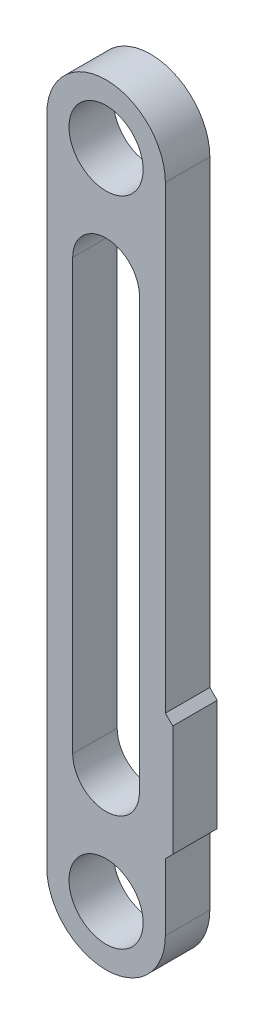
SolidWorks part; units mm, degrees
material "玻纤"
ref_plane "前视基准面" through (0, 0, 0) normal (0, 0, 1) x (1, 0, 0)
ref_plane "上视基准面" through (0, 0, 0) normal (0, 1, 0) x (1, 0, 0)
ref_plane "右视基准面" through (0, 0, 0) normal (1, 0, 0) x (0, 0, -1)
sketch "草图1" plane through (0, 0, 0) normal (0, 0, 1) x (1, 0, 0)
  line L0 (0, 0) -> (0, 88) construction
  line L1 (-8, 0) -> (-8, 88)
  line L2 (8, 0) -> (8, 88)
  arc A0 (-8, 0) -> (8, 0) centre (0, 0) ccw
  arc A1 (8, 88) -> (-8, 88) centre (0, 88) ccw
  circle A2 centre (0, 88) radius 5
  circle A3 centre (0, 0) radius 5
  point P3 (0, 44)
  dimension "D2" = 8
  dimension "D3" = 10
  dimension "D1" = 88
extrude "凸台-拉伸1" add sketch "草图1" along normal blind 6
sketch "草图2" plane through (0, 0, 0) normal (0, 0, -1) x (-1, 0, 0)
  line L0 (0, 73) -> (0, 15) construction
  line L1 (4.5, 73) -> (4.5, 15)
  line L2 (-4.5, 73) -> (-4.5, 15)
  line L3 (8, 88) -> (8, 0) construction
  arc A0 (4.5, 73) -> (-4.5, 73) centre (0, 73) ccw
  arc A1 (-4.5, 15) -> (4.5, 15) centre (0, 15) ccw
  circle A2 centre (0, 88) radius 5 construction
  point P3 (0, 44)
  dimension "D3" = 15
  dimension "D1" = 3.5
  dimension "D2" = 15
extrude "切除-拉伸1" cut sketch "草图2" against normal blind 10
sketch "草图3" plane through (0, 0, 6) normal (0, 0, 1) x (1, 0, 0)
  line L0 (9, 25) -> (8, 25)
  line L2 (8, 25) -> (8, 10)
  line L3 (8, 10) -> (9, 10)
  line L4 (9, 10) -> (9, 25)
  line L5 (8, 0) -> (8, 88) construction
  dimension "D1" = 15
  dimension "D2" = 1
  dimension "D3" = 10
extrude "凸台-拉伸2" add sketch "草图3" against normal up to surface (6 mm away) up to face at (0, 44, 0)
chamfer "倒角1" distance 1 angle 45 2 edges at (8, 10, 3) (8, 25, 3)
